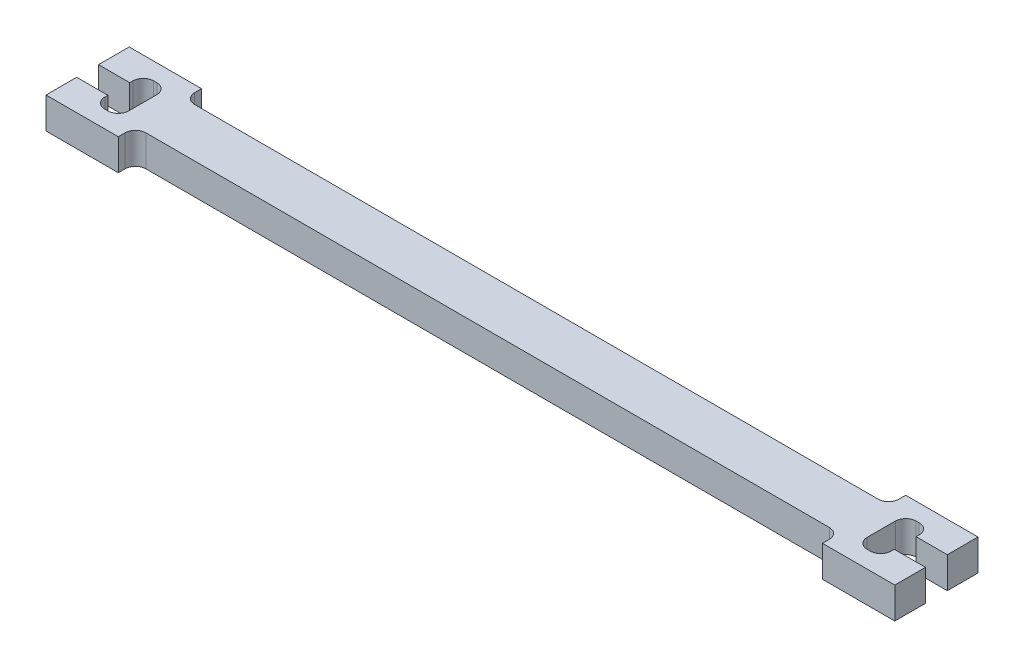
SolidWorks part; units mm, degrees
ref_plane "Front Plane" through (0, 0, 0) normal (0, 0, 1) x (1, 0, 0)
ref_plane "Top Plane" through (0, 0, 0) normal (0, 1, 0) x (1, 0, 0)
ref_plane "Right Plane" through (0, 0, 0) normal (1, 0, 0) x (0, 0, -1)
sketch "Sketch1" plane through (0, 0, 0) normal (0, 1, 0) x (1, 0, 0)
  line L0 (-40.8, 0) -> (40.8, 0) construction
  line L1 (-40.8, 4) -> (40.8, 4)
  line L2 (-40.8, 4) -> (-40.8, -4)
  line L3 (-40.8, -4) -> (40.8, -4)
  line L4 (40.8, 4) -> (40.8, -4)
  line L5 (-40.8, 4) -> (40.8, -4) construction
  line L6 (-40.8, -4) -> (40.8, 4) construction
  line L7 (-35.5, 2.35) -> (-35.5, 4) construction
  line L8 (-40.8, 1.05) -> (-37.8, 1.05)
  line L9 (-40.8, 1.05) -> (-40.8, -1.05)
  line L10 (-40.8, -1.05) -> (-37.8, -1.05)
  line L11 (-37.8, 1.05) -> (-37.8, -1.05)
  line L12 (-40.8, 1.05) -> (-37.8, -1.05) construction
  line L13 (-40.8, -1.05) -> (-37.8, 1.05) construction
  line L14 (-37.8, 2.35) -> (-35.5, 2.35)
  line L15 (-37.8, 2.35) -> (-37.8, -2.35)
  line L16 (-37.8, -2.35) -> (-35.5, -2.35)
  line L17 (-35.5, 2.35) -> (-35.5, -2.35)
  line L18 (-37.8, 2.35) -> (-35.5, -2.35) construction
  line L19 (-37.8, -2.35) -> (-35.5, 2.35) construction
  line L20 (-33.85, 2.35) -> (33.85, 2.35)
  line L21 (-33.85, 2.35) -> (-33.85, -2.35)
  line L22 (-33.85, -2.35) -> (33.85, -2.35)
  line L23 (33.85, 2.35) -> (33.85, -2.35)
  line L24 (-33.85, 2.35) -> (33.85, -2.35) construction
  line L25 (-33.85, -2.35) -> (33.85, 2.35) construction
  line L26 (-35.5, 2.35) -> (-33.85, 2.35) construction
  line L27 (-33.85, 2.35) -> (-33.85, 4)
  line L28 (-33.85, -2.35) -> (-33.85, -4)
  line L29 (0, 4) -> (0, -4) construction
  line L30 (33.85, -2.35) -> (33.85, -4)
  line L31 (-40.8, 4) -> (-40.8, -4)
  line L32 (40.8, 4) -> (40.8, -4)
  line L33 (33.85, 2.35) -> (33.85, 4)
  line L34 (40.8, -1.05) -> (37.8, -1.05)
  line L35 (37.8, -2.35) -> (35.5, -2.35)
  line L36 (35.5, 2.35) -> (35.5, -2.35)
  line L37 (37.8, 2.35) -> (35.5, 2.35)
  line L38 (37.8, 2.35) -> (37.8, -2.35)
  line L39 (40.8, 1.05) -> (37.8, 1.05)
  point P0 (0, 0)
  point P8 (-39.3, 0)
  point P13 (-36.65, 0)
  point P18 (0, 0)
  dimension "D1" = 8
  dimension "D2" = 81.6
  dimension "D3" = 3
  dimension "D4" = 2.3
  dimension "D5" = 4.7
  dimension "D6" = 2.1
extrude "Base shape" add sketch "Sketch1" along normal blind 3 contours L23 L20 L21 L22 | L28 L21 L27 L1 L2 L8 L15 L14 L17 L16 L10 L3 | L39 L4 L1 L33 L23 L30 L3 L32 L34 L38 L35 L36 L37 region at (-37.325, 0, -3.894) region at (37.325, 0, -3.894) region at (0, 0, 0)
fillet "Milling fillets" radius 1 12 edges at (37.8, 1.5, 2.35) (-35.5, 1.5, 2.35) (-37.8, 1.5, 2.35) (35.5, 1.5, 2.35) (35.5, 1.5, -2.35) (-37.8, 1.5, -2.35) (-35.5, 1.5, -2.35) (37.8, 1.5, -2.35) (33.85, 1.5, 2.35) (33.85, 1.5, -2.35) (-33.85, 1.5, -2.35) (-33.85, 1.5, 2.35)
sketch "Center axis sketch" plane through (40.8, 0, 0) normal (1, 0, 0) x (0, 0, -1)
  line L0 (-1.05, 0) -> (1.05, 3) construction
  point P4 (0, 1.5)
ref_axis "Center axis" through (-46.4653, 1.5, 0) along (1, 0, 0)
